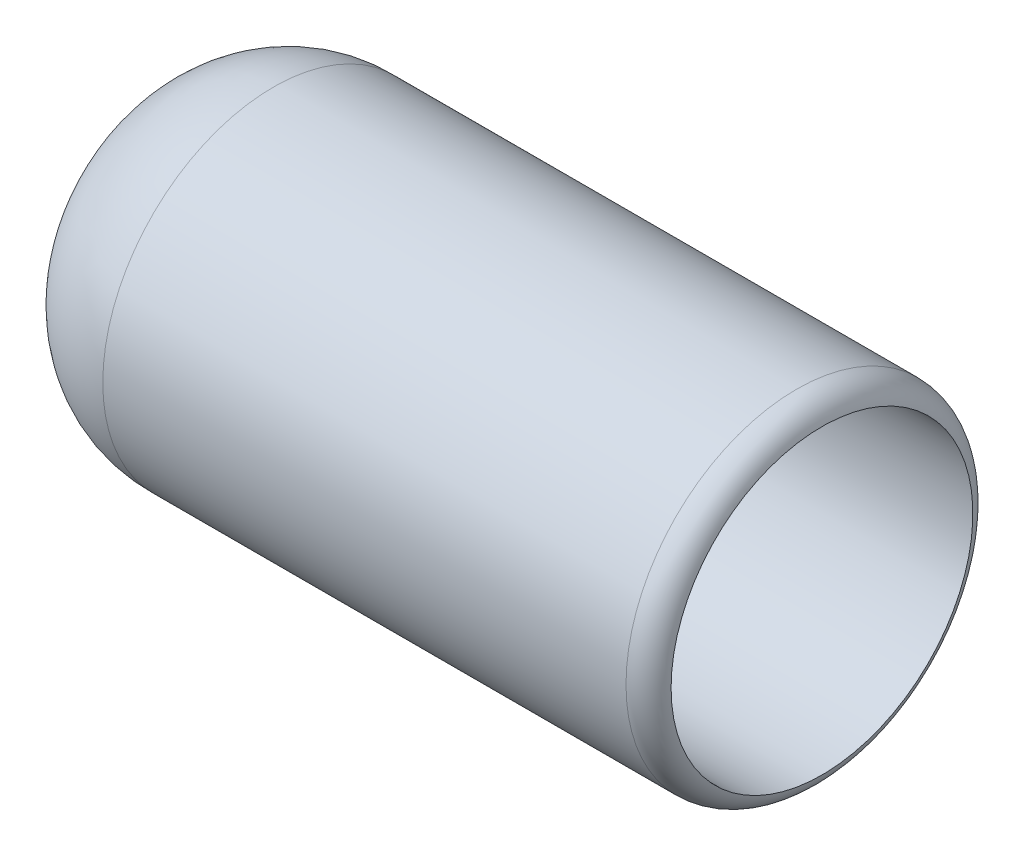
SolidWorks part; units mm, degrees
ref_plane "Front Plane" through (0, 0, 0) normal (0, 0, 1) x (1, 0, 0)
ref_plane "Top Plane" through (0, 0, 0) normal (0, 1, 0) x (1, 0, 0)
ref_plane "Right Plane" through (0, 0, 0) normal (1, 0, 0) x (0, 0, -1)
sketch "Sketch1" plane through (0, 0, 0) normal (0, 0, 1) x (1, 0, 0)
  line L0 (8.1848, 13) -> (50, 13)
  line L1 (8.1848, 11.5) -> (50, 11.5)
  line L2 (55, 0) -> (-55, 0) construction
  line L3 (50, 13) -> (50, 11.5)
  line L4 (0, -55) -> (0, 55) construction
  line L6 (0, 9.0017) -> (0, 7.5017)
  line L7 (0, 0) -> (47.9238, 0) construction
  arc A2 (8.1848, 11.5) -> (0, 7.5017) centre (8, 1.5017) ccw
  arc A3 (8.1848, 13) -> (0, 9.0017) centre (8, 3.0017) ccw
  dimension "D4" = 10
  dimension "D5" = 10
  dimension "D1" = 11.5
  dimension "D2" = 13
  dimension "D3" = 50
  dimension "D6" = 1.5017
  dimension "D7" = 8
revolve "Revolve1" add sketch "Sketch1" angle 360 about L7
fillet "Fillet2" radius 2 1 edges at (50, 0, 13)
